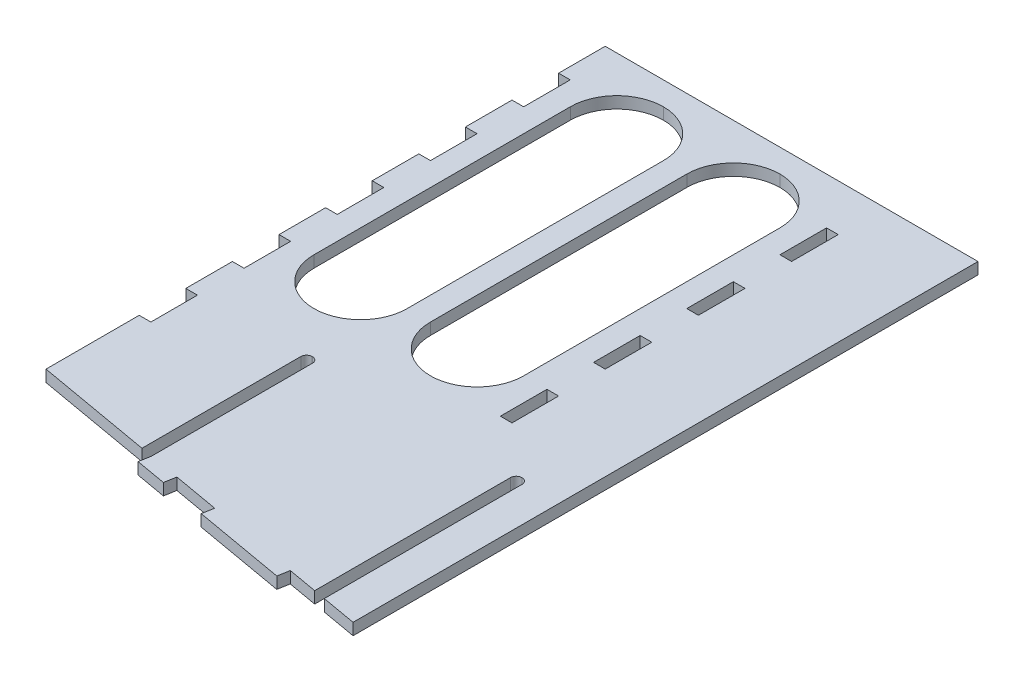
SolidWorks part; units mm, degrees
ref_plane "Front Plane" through (0, 0, 0) normal (0, 0, 1) x (1, 0, 0)
ref_plane "Top Plane" through (0, 0, 0) normal (0, 1, 0) x (1, 0, 0)
ref_plane "Right Plane" through (0, 0, 0) normal (1, 0, 0) x (0, 0, -1)
sketch "Sketch1" plane through (0, 0, 0) normal (0, 1, 0) x (1, 0, 0)
  line L0 (0, 0) -> (101.6, -17.9148)
  line L1 (0, 0) -> (101.6, 0)
  line L2 (0, 0) -> (0, 152.4)
  line L3 (0, 152.4) -> (101.6, 152.4)
  line L4 (101.6, 0) -> (101.6, 152.4)
  line L5 (101.6, -17.9148) -> (101.6, 0)
  dimension "D1" = 101.6
  dimension "D2" = 152.4
  dimension "D3" = 10
extrude "Boss-Extrude1" add sketch "Sketch1" along normal blind 3.175 contours L1 L4 L3 L2 | L0 L5 L1 region at (67.7333, 0, 5.9716) region at (50.8, 0, -76.2)
sketch "Sketch2" plane through (0, 3.175, 0) normal (0, 1, 0) x (1, 0, 0)
  line L0 (0, 0) -> (0, 152.4) construction
  line L1 (0, 139.7) -> (3.175, 139.7)
  line L2 (0, 139.7) -> (0, 127)
  line L3 (0, 127) -> (3.175, 127)
  line L4 (3.175, 139.7) -> (3.175, 127)
  line L5 (0, 152.4) -> (101.6, 152.4) construction
  dimension "D1" = 3.175
  dimension "D2" = 12.7
  dimension "D3" = 12.7
extrude "Cut-Extrude1" cut sketch "Sketch2" against normal blind 3.175
pattern_linear "LPattern1" count 5 spacing 25.4 along (0, 0, 1) of "Cut-Extrude1"
sketch "Sketch3" plane through (0, 3.175, 0) normal (0, 1, 0) x (1, 0, 0)
  line L0 (101.6, -17.9148) -> (101.6, 152.4) construction
  line L1 (76.2, 139.7) -> (73.025, 139.7)
  line L2 (76.2, 139.7) -> (76.2, 127)
  line L3 (76.2, 127) -> (73.025, 127)
  line L4 (73.025, 139.7) -> (73.025, 127)
  line L5 (0, 152.4) -> (101.6, 152.4) construction
  dimension "D1" = 3.175
  dimension "D2" = 12.7
  dimension "D3" = 25.4
  dimension "D4" = 12.7
extrude "Cut-Extrude2" cut sketch "Sketch3" against normal blind 3.175
pattern_linear "LPattern2" count 4 spacing 25.4 along (0, 0, 1) of "Cut-Extrude2"
sketch "BallVisualization" plane through (0, 3.175, 0) normal (0, 1, 0) x (1, 0, 0)
  circle A0 centre (33.8021, 16.6688) radius 21.59
  circle A1 centre (142.2868, -2.9508) radius 21.59
  circle A2 centre (106.0483, 3.2813) radius 21.59
  circle A3 centre (70.5023, 9.2826) radius 21.59
  circle A4 centre (52.0368, 48.2909) radius 21.59
  circle A5 centre (25.031, 65.8331) radius 21.59
  circle A6 centre (52.0368, 90.9923) radius 21.59
  circle A7 centre (25.031, 112.5823) radius 21.59
  circle A8 centre (50.7294, 133.5447) radius 21.59
  circle A9 centre (22.5412, 155.1347) radius 21.59
  point P2 (48.5998, 14.0387)
  point P5 (26.5977, 51.8423)
  point P8 (51.2, 88.4458)
  point P11 (24.9975, 124.0492)
  point P12 (73.6532, 9.2465)
  point P13 (0, 0)
  point P14 (109.1104, 3.3338)
  point P15 (152.7496, -4.8555)
  point P16 (64.9947, 10.9296)
  point P17 (26.7623, 17.9663)
  point P18 (71.1732, 9.4749)
  point P19 (115.4465, 3.3057)
  point P20 (158.6111, -4.838)
  point P21 (114.8762, 3.1961)
  point P22 (48.2267, 59.6696)
  point P23 (131.1514, 0)
  point P24 (142.2868, -2.9508)
  point P25 (98.2005, 4.4354)
  point P26 (99.3546, 4.6662)
  point P27 (56.6532, 12.0524)
  point P28 (25.9543, 42.0588)
  point P31 (0, 0)
  point P32 (51.5752, 67.218)
  point P33 (106.0483, 3.2813)
  point P34 (70.5023, 9.2826)
  point P35 (33.8021, 16.6688)
  point P36 (52.0368, 48.2909)
  point P39 (25.031, 65.8331)
  point P42 (52.0368, 90.9923)
  point P45 (25.031, 112.5823)
  point P50 (22.5412, 155.1347)
  dimension "D1" = 43.18
sketch "Sketch5" plane through (0, 3.175, 0) normal (0, 1, 0) x (1, 0, 0)
  line L0 (101.6, -17.9148) -> (101.6, 152.4) construction
  line L1 (31.75, 39.2352) -> (34.925, 39.2352)
  line L2 (31.75, 39.2352) -> (31.75, -17.9148)
  line L3 (31.75, -17.9148) -> (34.925, -17.9148)
  line L4 (34.925, 39.2352) -> (34.925, -17.9148)
  line L5 (88.9, 39.2352) -> (92.075, 39.2352)
  line L6 (88.9, 39.2352) -> (88.9, -17.9148)
  line L7 (88.9, -17.9148) -> (92.075, -17.9148)
  line L8 (92.075, 39.2352) -> (92.075, -17.9148)
  point P11 (58.8129, 19.9949)
  dimension "D1" = 57.15
  dimension "D2" = 57.15
  dimension "D3" = 3.175
  dimension "D4" = 3.175
  dimension "D5" = 0
  dimension "D6" = 9.525
  dimension "D7" = 0
  dimension "D8" = 53.975
extrude "Cut-Extrude3" cut sketch "Sketch5" against normal blind 3.175
fillet "Fillet1" radius 1.524 4 edges at (88.9, 1.5875, -39.2352) (92.075, 1.5875, -39.2352) (34.925, 1.5875, -39.2352) (31.75, 1.5875, -39.2352)
sketch "Sketch6" plane through (0, 3.175, 0) normal (0, 1, 0) x (1, 0, 0)
  line L0 (34.925, -6.1582) -> (43.3047, -7.6358)
  line L1 (34.925, -6.1582) -> (88.9, -15.6755) construction
  line L2 (43.3047, -7.6358) -> (42.7534, -10.7626)
  line L3 (42.7534, -10.7626) -> (34.3737, -9.285)
  line L4 (34.3737, -9.285) -> (34.925, -6.1582)
  line L5 (55.8118, -9.8411) -> (80.8259, -14.2518)
  line L6 (80.8259, -14.2518) -> (80.2746, -17.3786)
  line L7 (80.2746, -17.3786) -> (55.2605, -12.9679)
  line L8 (55.2605, -12.9679) -> (55.8118, -9.8411)
  dimension "D1" = 8.509
  dimension "D2" = 3.175
  dimension "D3" = 0
  dimension "D4" = 3.175
  dimension "D5" = 25.4
  dimension "D6" = 12.7
extrude "Boss-Extrude2" add sketch "Sketch6" against normal blind 3.175
sketch "Sketch7" plane through (0, 3.175, 0) normal (0, 1, 0) x (1, 0, 0)
  line L0 (3.175, 101.6) -> (3.175, 114.3) construction
  line L1 (9.525, 146.05) -> (34.925, 146.05)
  line L2 (9.525, 146.05) -> (9.525, 50.8)
  line L3 (9.525, 50.8) -> (34.925, 50.8)
  line L4 (34.925, 146.05) -> (34.925, 50.8)
  line L5 (41.275, 146.05) -> (66.675, 146.05)
  line L6 (41.275, 146.05) -> (41.275, 50.8)
  line L7 (41.275, 50.8) -> (66.675, 50.8)
  line L8 (66.675, 146.05) -> (66.675, 50.8)
  line L9 (73.025, 139.7) -> (73.025, 127) construction
  line L10 (0, 152.4) -> (101.6, 152.4) construction
  dimension "D1" = 95.25
  dimension "D2" = 95.25
  dimension "D3" = 25.4
  dimension "D4" = 25.4
  dimension "D5" = 6.35
  dimension "D6" = 6.35
  dimension "D7" = 6.35
  dimension "D8" = 6.35
extrude "Cut-Extrude4" cut sketch "Sketch7" against normal blind 3.175
fillet "Fillet2" radius 12.7 8 edges at (66.675, 1.5875, -146.05) (34.925, 1.5875, -146.05) (41.275, 1.5875, -146.05) (9.525, 1.5875, -146.05) (34.925, 1.5875, -50.8) (41.275, 1.5875, -50.8) (66.675, 1.5875, -50.8) (9.525, 1.5875, -50.8)
